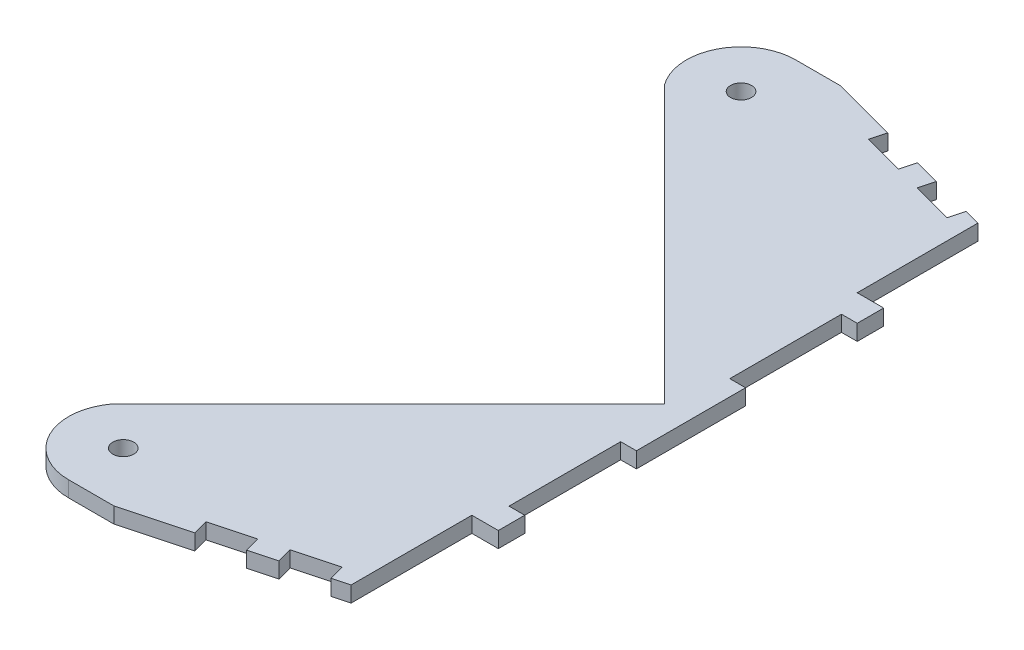
SolidWorks part; units mm, degrees
ref_plane "Front" through (0, 0, 0) normal (0, 0, 1) x (1, 0, 0)
ref_plane "Top" through (0, 0, 0) normal (0, 1, 0) x (1, 0, 0)
ref_plane "Right" through (0, 0, 0) normal (1, 0, 0) x (0, 0, -1)
ref_axis "side-side" through (80.9, 0, 0) along (-1, 0, 0)
ref_axis "up-down" through (0, 50, 0) along (0, -1, 0)
ref_axis "front-back" through (0, 0, -80.9) along (0, 0, 1)
sketch "Sketch1" plane through (0, 0, 0) normal (0, 1, 0) x (1, 0, 0)
  line L1 (0, 0) -> (-83.6295, 83.6295)
  line L3 (0, -94.8336) -> (-56.6019, -110)
  line L4 (-56.6019, 110) -> (0, 94.8336)
  line L5 (-70.3102, 110) -> (-56.6019, 110)
  line L6 (8, 58.293) -> (8, -58.293)
  line L7 (0, 0) -> (58.8362, 0) construction
  line L8 (-70.3102, -110) -> (-56.6019, -110)
  line L10 (0, 0) -> (-83.6295, -83.6295)
  line L12 (0, 94.8336) -> (0, 58.293)
  line L13 (0, 58.293) -> (8, 58.293)
  line L16 (0, -94.8336) -> (0, -58.293)
  line L17 (0, -58.293) -> (8, -58.293)
  circle A0 centre (-70.3102, 93.4511) radius 3.175
  circle A1 centre (-70.3102, -93.4511) radius 3.175
  arc A2 (-83.6295, 83.6295) -> (-70.3102, 110) centre (-70.3102, 93.4511) cw
  arc A3 (-83.6295, -83.6295) -> (-70.3102, -110) centre (-70.3102, -93.4511) ccw
  dimension "D5" = 6.35
  dimension "D1" = 64.6019
  dimension "D2" = 110
  dimension "D3" = 8
  dimension "D4" = 45
  dimension "D6" = 75
  dimension "D7" = 116.586
  dimension "D8" = 8
extrude "Boss-Extrude1" add sketch "Sketch1" along normal blind 4.7625
chamfer "Chamfer1" [suppressed] distance 10 distance2 10
sketch "Sketch3" plane through (0, 0, 0) normal (0, 1, 0) x (1, 0, 0)
  line L0 (-37.2834, 104.8236) -> (-24.9202, 101.5109)
  line L1 (-37.2834, 104.8236) -> (-38.5161, 100.2234)
  line L2 (-24.9202, 101.5109) -> (-26.1529, 96.9107)
  line L3 (-38.5161, 100.2234) -> (-26.1529, 96.9107)
  line L4 (-17.1928, 99.4404) -> (-4.8296, 96.1276)
  line L5 (-17.1928, 99.4404) -> (-18.4255, 94.8401)
  line L6 (-4.8296, 96.1276) -> (-6.0623, 91.5274)
  line L7 (-18.4255, 94.8401) -> (-6.0623, 91.5274)
  line L8 (-56.6019, 110) -> (0, 94.8336) construction
  line L9 (-6.1395, 91.5481) -> (-38.4388, 100.2027) construction
  line L10 (0, 0) -> (58.8362, 0) construction
  line L11 (0, 0) -> (58.8362, 0) construction
  line L12 (-18.4255, -94.8401) -> (-6.0623, -91.5274)
  line L13 (-4.8296, -96.1276) -> (-6.0623, -91.5274)
  line L14 (-17.1928, -99.4404) -> (-18.4255, -94.8401)
  line L15 (-17.1928, -99.4404) -> (-4.8296, -96.1276)
  line L16 (-38.5161, -100.2234) -> (-26.1529, -96.9107)
  line L17 (-24.9202, -101.5109) -> (-26.1529, -96.9107)
  line L18 (-37.2834, -104.8236) -> (-38.5161, -100.2234)
  line L19 (-37.2834, -104.8236) -> (-24.9202, -101.5109)
  line L20 (3.2375, 53.213) -> (3.2375, -53.213) construction
  line L21 (8, 50.293) -> (3.2375, 50.293)
  line L22 (8, 50.293) -> (8, 16.51)
  line L23 (8, 16.51) -> (3.2375, 16.51)
  line L24 (3.2375, 50.293) -> (3.2375, 16.51)
  line L25 (3.2375, -50.293) -> (3.2375, -16.51)
  line L26 (8, -16.51) -> (3.2375, -16.51)
  line L27 (8, -50.293) -> (8, -16.51)
  line L28 (8, -50.293) -> (3.2375, -50.293)
  line L29 (8, 58.293) -> (0, 58.293) construction
  point P32 (0, 0)
  point P33 (0, 0)
  point P39 (0, 0)
  dimension "D1" = 8
extrude "Cut-Extrude2" cut sketch "Sketch3" along normal blind 10
